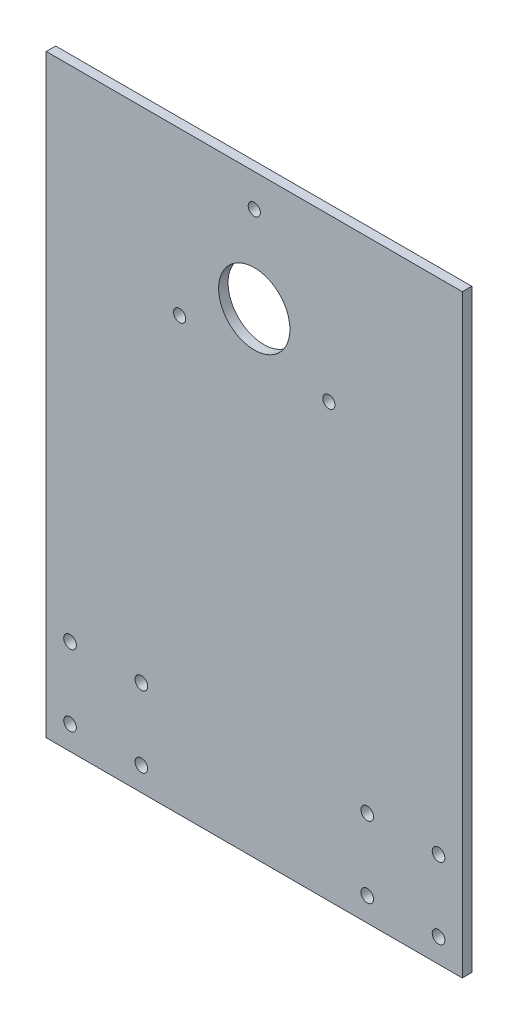
SolidWorks part; units mm, degrees
ref_plane "Front Plane" through (0, 0, 0) normal (0, 0, 1) x (1, 0, 0)
ref_plane "Top Plane" through (0, 0, 0) normal (0, 1, 0) x (1, 0, 0)
ref_plane "Right Plane" through (0, 0, 0) normal (1, 0, 0) x (0, 0, -1)
sketch "Sketch1" plane through (0, 0, 0) normal (0, 0, 1) x (1, 0, 0)
  line L0 (0, 100) -> (0, -100) construction
  line L1 (-70, -100) -> (70, -100)
  line L2 (-70, -100) -> (-70, 100)
  line L3 (-70, 100) -> (70, 100)
  line L4 (70, -100) -> (70, 100)
  line L5 (-70, -100) -> (70, 100) construction
  line L6 (-70, 100) -> (70, -100) construction
  line L7 (-50, -95.8304) -> (-50, -78.0714) construction
  line L10 (-62, -80) -> (-36.3402, -80) construction
  circle A0 centre (0, 60) radius 33.35 construction
  circle A1 centre (0, 60) radius 29 construction
  circle A2 centre (0, 89) radius 2.05
  circle A3 centre (25.1147, 45.5) radius 2.05
  circle A4 centre (-25.1147, 45.5) radius 2.05
  circle A10 centre (0, 60) radius 12
  circle A11 centre (-62, -92) radius 2.125
  circle A12 centre (-38, -92) radius 2.125
  circle A13 centre (-38, -68) radius 2.125
  circle A14 centre (-62, -68) radius 2.125
  circle A15 centre (38, -92) radius 2.125
  circle A16 centre (62, -92) radius 2.125
  circle A17 centre (62, -68) radius 2.125
  circle A18 centre (38, -68) radius 2.125
  point P0 (0, 0)
  point P19 (0, 60)
  dimension "D3" = 66.7
  dimension "D4" = 40
  dimension "D5" = 58
  dimension "D6" = 4.1
  dimension "D8" = 4.25
  dimension "D9" = 8
  dimension "D10" = 8
  dimension "D12" = 24
  dimension "D1" = 140
  dimension "D2" = 200
  dimension "D11" = 12
  dimension "D13" = 12
  dimension "D7" = 3
extrude "Boss-Extrude1" add sketch "Sketch1" along normal blind 3.175
